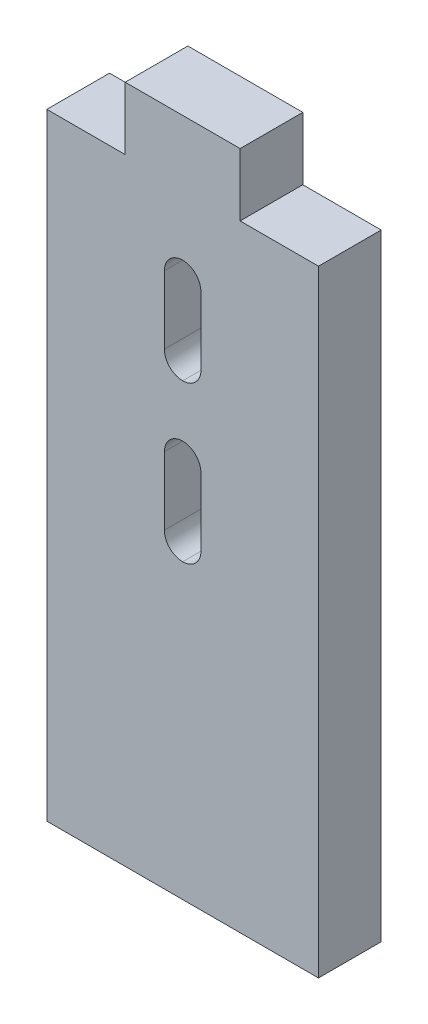
SolidWorks part; units mm, degrees
material "Acrílico (médio-alto impacto)"
ref_plane "Front" through (0, 0, 0) normal (0, 0, 1) x (1, 0, 0)
ref_plane "Top" through (0, 0, 0) normal (0, 1, 0) x (1, 0, 0)
ref_plane "Right" through (0, 0, 0) normal (1, 0, 0) x (0, 0, -1)
sketch "Esboço1" plane through (0, 0, 0) normal (0, 0, 1) x (1, 0, 0)
  line L0 (0, 32.5) -> (-5.5, 32.5)
  line L1 (13, -32.5) -> (-13, -32.5)
  line L2 (13, -32.5) -> (13, 32.5)
  line L3 (13, 32.5) -> (-13, 32.5)
  line L4 (-13, -32.5) -> (-13, 32.5)
  line L5 (13, -32.5) -> (-13, 32.5) construction
  line L6 (13, 32.5) -> (-13, -32.5) construction
  line L7 (-5.5, 32.5) -> (-13, 32.5)
  line L8 (0, 32.5) -> (5.5, 32.5)
  line L9 (5.5, 32.5) -> (13, 32.5)
  line L10 (13, 32.5) -> (13, 26.5)
  line L11 (13, 26.5) -> (5.5, 26.5)
  line L12 (5.5, 26.5) -> (5.5, 32.5)
  line L13 (-13, 32.5) -> (-13, 26.5)
  line L14 (-13, 26.5) -> (-5.5, 26.5)
  line L15 (-5.5, 26.5) -> (-5.5, 32.5)
  line L16 (0, 32.5) -> (0, -32.5) construction
  line L17 (0, 32.5) -> (0, 20.5) construction
  line L18 (0, 20.5) -> (0, 10.5) construction
  line L19 (0, 10.5) -> (0, 5.5) construction
  line L20 (0, 5.5) -> (0, -4.5) construction
  line L21 (1.75, 20.5) -> (-1.75, 20.5)
  line L22 (1.75, 10.5) -> (-1.75, 10.5)
  line L23 (1.75, 5.5) -> (-1.75, 5.5)
  line L24 (1.75, -4.5) -> (-1.75, -4.5)
  line L25 (-1.75, 20.5) -> (-1.75, 10.5)
  line L26 (1.75, 20.5) -> (1.75, 10.5)
  line L27 (1.75, 5.5) -> (1.75, -4.5)
  line L28 (-1.75, 5.5) -> (-1.75, -4.5)
  point P0 (0, 0)
  point P21 (0, 20.5)
  point P24 (0, 10.5)
  point P27 (0, 5.5)
  point P30 (0, -4.5)
  dimension "D1" = 26
  dimension "D2" = 65
  dimension "D3" = 12
  dimension "D4" = 10
  dimension "D5" = 5
  dimension "D6" = 28
  dimension "D7" = 10
  dimension "D8" = 3.5
extrude "Ressalto-extrusão1" add sketch "Esboço1" along normal blind 6 contours L15 L14 L4 L1 L2 L11 L12 L3 L0 L28 L23 L27 L24 L21 L26 L22 L25 region at (2.75, 31.7999, 0)
fillet "Filete1" radius 1.75 8 edges at (-1.75, -4.5, 3) (1.75, -4.5, 3) (1.75, 5.5, 3) (-1.75, 5.5, 3) (1.75, 10.5, 3) (-1.75, 10.5, 3) (1.75, 20.5, 3) (-1.75, 20.5, 3)
